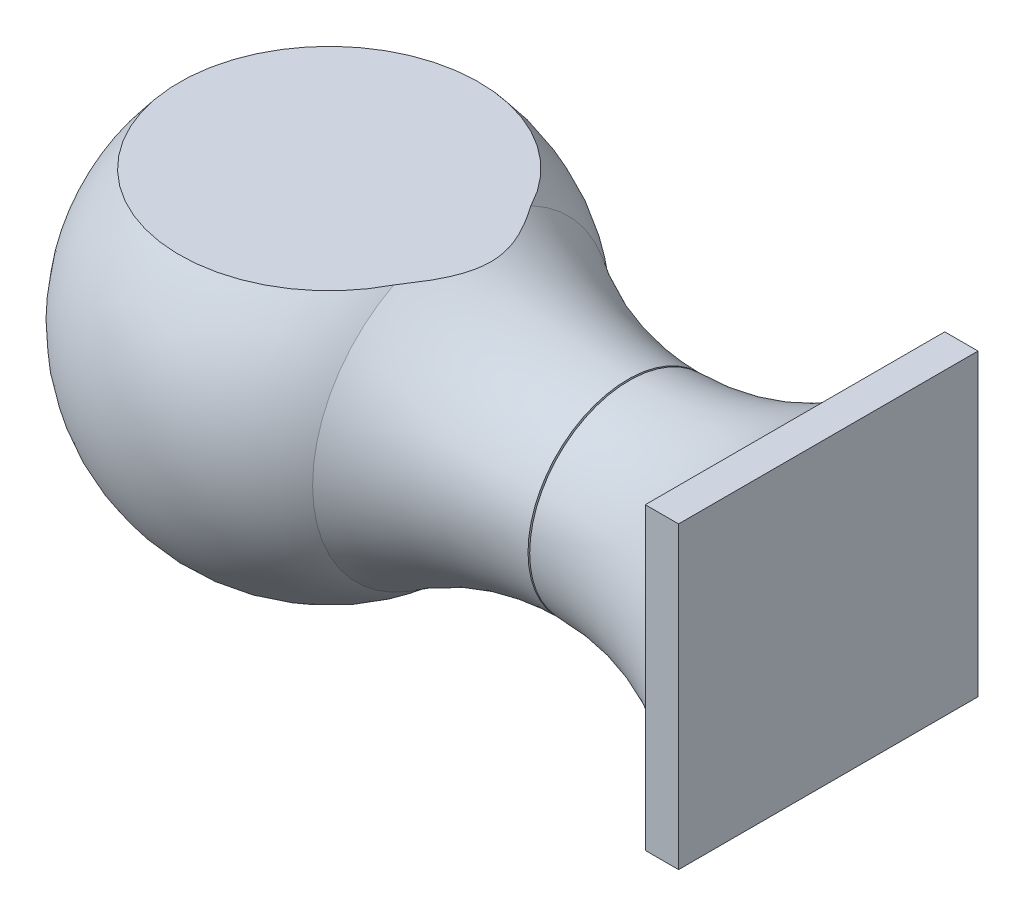
SolidWorks part; units mm, degrees
ref_plane "Front Plane" through (0, 0, 0) normal (0, 0, 1) x (1, 0, 0)
ref_plane "Top Plane" through (0, 0, 0) normal (0, 1, 0) x (1, 0, 0)
ref_plane "Right Plane" through (0, 0, 0) normal (1, 0, 0) x (0, 0, -1)
sketch "Sketch2" plane through (0, 0, 0) normal (0, 1, 0) x (1, 0, 0)
  line L0 (-50, 0) -> (-0.25, 0)
  line L2 (-50, 45) -> (-50, 0)
  line L4 (50, 45) -> (50, 0)
  line L5 (-50, 45) -> (50, -45) construction
  line L6 (-50, -45) -> (50, 45) construction
  line L7 (0.25, 30.0003) -> (0.25, 0)
  line L8 (0, 53.0822) -> (0, -19.8884) construction
  line L9 (-0.25, 30.0003) -> (-0.25, 0)
  line L10 (0.25, 0) -> (50, 0)
  arc A0 (-50, 45) -> (-0.25, 30.0003) centre (0, 120.8333) ccw
  arc A1 (0.25, 30.0003) -> (50, 45) centre (0, 120.8333) ccw
  point P0 (0, 0)
  dimension "D1" = 100
  dimension "D2" = 90
  dimension "D4" = 45
  dimension "D5" = 100
  dimension "D6" = 50
  dimension "D7" = 50
  dimension "D8" = 45
  dimension "D9" = 0.5
revolve "Revolve1" add sketch "Sketch2" angle 360 about L0
sketch "Sketch3" plane through (50, 0, 0) normal (1, 0, 0) x (0, 0, -1)
  line L1 (-45, 45) -> (45, 45)
  line L2 (-45, 45) -> (-45, -45)
  line L3 (-45, -45) -> (45, -45)
  line L4 (45, 45) -> (45, -45)
  line L5 (-45, 45) -> (45, -45) construction
  line L6 (-45, -45) -> (45, 45) construction
  circle A0 centre (0, 0) radius 45 construction
  point P0 (0, 0)
  point P6 (0, -45)
  point P9 (45, 0)
extrude "Boss-Extrude1" add sketch "Sketch3" along normal blind 10
sketch "Sketch5" plane through (0, 0, 0) normal (0, 1, 0) x (1, 0, 0)
  line L0 (-150.208, 0) -> (-29.792, 0)
  arc A0 (-29.792, 0) -> (-150.208, 0) centre (-90, 0) ccw
  dimension "D1" = 90
revolve "Revolve8" add sketch "Sketch5" angle 360 about L0
ref_plane "Plane3" through (0, 60, 0) normal (0, 1, 0) x (1, 0, 0)
sketch "Sketch7" plane through (0, 60, 0) normal (0, 1, 0) x (1, 0, 0)
  line L1 (-157.7319, 66.6548) -> (-25.6682, 66.6548)
  line L2 (-157.7319, 66.6548) -> (-157.7319, -66.6548)
  line L3 (-157.7319, -66.6548) -> (-25.6682, -66.6548)
  line L4 (-25.6682, 66.6548) -> (-25.6682, -66.6548)
  line L5 (-157.7319, 66.6548) -> (-25.6682, -66.6548) construction
  line L6 (-157.7319, -66.6548) -> (-25.6682, 66.6548) construction
  point P0 (-91.7001, 0)
extrude "Cut-Extrude1" cut sketch "Sketch7" against normal blind 20 and the other way blind 20
